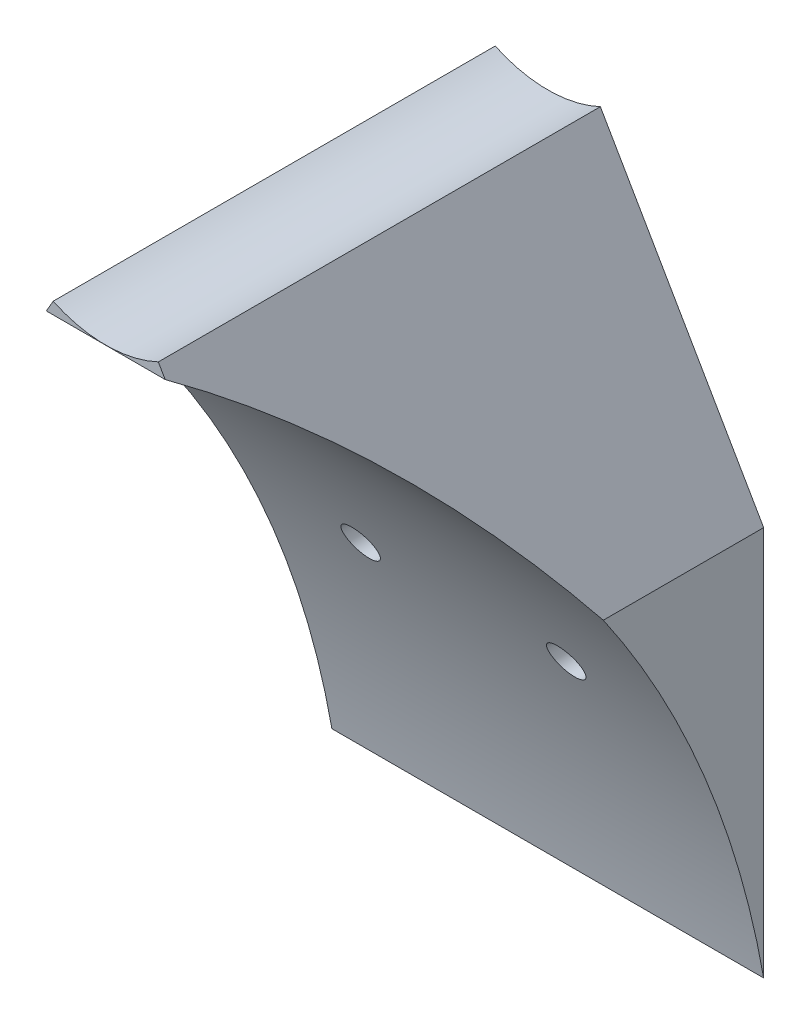
SolidWorks part; units mm, degrees
material "ABS"
ref_plane "Front Plane" through (0, 0, 0) normal (0, 0, 1) x (1, 0, 0)
ref_plane "Top Plane" through (0, 0, 0) normal (0, 1, 0) x (1, 0, 0)
ref_plane "Right Plane" through (0, 0, 0) normal (1, 0, 0) x (0, 0, -1)
sketch "Sketch1" plane through (0, 0, 0) normal (0, 0, 1) x (1, 0, 0)
  line L0 (0, 0) -> (0, -127) construction
  line L1 (0, 0) -> (38.1, -65.9911) construction
  line L2 (0, 0) -> (-38.1, -65.9911) construction
  line L3 (-38.1, -65.9911) -> (-38.1, -121.1503) construction
  line L5 (0, 0) -> (0, -127) construction
  line L6 (38.1, -121.1503) -> (38.1, -65.9911) construction
  line L7 (38.1, -121.1503) -> (38.1, -159.2503) construction
  line L8 (-50.8, -197.3503) -> (0, -197.3503) construction
  line L9 (-50.8, -195.7628) -> (0, -195.7628) construction
  line L10 (36.5125, -121.1503) -> (36.5125, -159.2503) construction
  line L11 (36.5125, -121.1503) -> (36.5125, -66.4165)
  line L12 (0, -3.175) -> (36.5125, -66.4165)
  line L13 (0, -3.175) -> (-36.5125, -66.4165)
  line L14 (-36.5125, -66.4165) -> (-36.5125, -121.1503)
  line L15 (-36.5125, -121.1503) -> (-38.1, -121.1503) construction
  line L16 (-50.8, -195.7628) -> (-50.8, -197.3503) construction
  line L17 (36.5125, -121.1503) -> (-36.5125, -121.1503)
  circle A0 centre (0, 0) radius 127 construction
  circle A1 centre (0, 0) radius 76.2 construction
  arc A2 (38.1, -159.2503) -> (0, -197.3503) centre (0, -159.2503) cw construction
  arc A3 (36.5125, -159.2503) -> (0, -195.7628) centre (0, -159.2503) cw construction
  point P2 (-15.875, -74.528)
  point P12 (0, 0)
  point P14 (15.875, -74.528)
  point P25 (0, -38.1)
  dimension "D2" = 152.4
  dimension "D6" = 1.5875
  dimension "D1" = 127
  dimension "D3" = 38.1
  dimension "D4" = 50.8
  dimension "D5" = 60
  dimension "D7" = 38.1
  dimension "D8" = 31.75
extrude "Boss-Extrude1" add sketch "Sketch1" along normal blind 76.2
sketch "Sketch2" plane through (0, 0, 0) normal (1, 0, 0) x (0, 0, -1)
  line L3 (-76.2, -121.1503) -> (0, -121.1503) construction
  line L4 (-76.2, -121.1503) -> (-76.2, -66.4165) construction
  line L6 (-76.2, -121.1503) -> (0, -121.1503)
  line L7 (-76.2, -121.1503) -> (-76.2, -66.4165)
  line L10 (-76.2, -66.4165) -> (-76.2, -3.175) construction
  line L11 (-76.2, -22.225) -> (-76.2, -66.4165)
  line L12 (0, -66.4165) -> (0, -3.175) construction
  line L13 (-76.2, -3.175) -> (0, -3.175) construction
  line L14 (-68.2625, -19.0675) -> (-68.2625, -3.175)
  line L15 (-68.2625, -3.175) -> (-76.2, -3.175)
  line L16 (-76.2, -3.175) -> (-76.2, -22.225)
  arc A0 (-68.2625, -19.0675) -> (0, -121.1503) centre (-150.0796, -147.6432) cw
  dimension "D1" = 68.2625
  dimension "D2" = 152.4
extrude "Cut-Extrude1" cut sketch "Sketch2" along normal up to surface (36.5125 mm away) from surface up to face at (36.5125, -93.7834, 38.1) starting at face at (-36.5125, -93.7834, 38.1)
sketch "Sketch5" plane through (0, 0, 0) normal (0, 0, 1) x (1, 0, 0)
  line L0 (0, -82.55) -> (0, 0) construction
  circle A0 centre (0, 0) radius 82.55 construction
  point P0 (0, -38.1)
  point P4 (-15.875, -81.0092)
  point P5 (15.875, -81.0092)
  dimension "D1" = 38.1
  dimension "D3" = 165.1
  dimension "D2" = 31.75
hole_wizard "M5 Clearance Hole1" positions "Sketch7" profile "Sketch8" hole size "M5" standard "ANSI Metric" end condition through all
sketch "Sketch7" plane through (0, 0, 0) normal (0, 0, -1) x (-1, 0, 0)
  point P0 (-15.875, -81.0092)
  point P3 (15.875, -81.0092)
  point P6 (0, -38.1)
sketch "Sketch8" plane through (15.875, -81.0092, 0) normal (1, 0, 0) x (0, 1, 0)
  line L0 (0, 0) -> (0, 68.2625)
  line L1 (0, 68.2625) -> (2.75, 68.2625)
  line L2 (2.75, 68.2625) -> (2.75, 0)
  line L5 (2.75, 0) -> (0, 0)
  line L11 (0, -6.35) -> (0, 107.95) construction
  dimension "Thru Hole Dia." = 5.5
  dimension "Thru Hole Depth" = 68.2625
sketch "Sketch10" plane through (0, 0, 0) normal (0, 0, -1) x (-1, 0, 0)
  circle A0 centre (0, 0) radius 19.05
  dimension "D1" = 38.1
extrude "Cut-Extrude2" cut sketch "Sketch10" against normal up to next
sketch "Sketch11" plane through (0, 0, 0) normal (0, 0, -1) x (-1, 0, 0)
  line L0 (-33.3375, -60.9172) -> (-33.3375, -121.1503)
  line L1 (-36.5125, -66.4165) -> (-8.1171, -17.2342) construction
  line L2 (36.5125, -121.1503) -> (-36.5125, -121.1503) construction
  line L3 (33.3375, -60.9172) -> (33.3375, -121.1503)
  line L4 (8.1171, -17.2342) -> (36.5125, -66.4165) construction
  line L5 (33.3375, -121.1503) -> (36.5125, -121.1503)
  line L10 (36.5125, -66.4165) -> (8.1171, -17.2342)
  line L11 (-8.1171, -17.2342) -> (-36.5125, -66.4165)
  line L12 (-36.5125, -66.4165) -> (-36.5125, -121.1503)
  line L13 (-36.5125, -121.1503) -> (36.5125, -121.1503)
  line L14 (36.5125, -121.1503) -> (36.5125, -66.4165)
  line L15 (36.5125, -66.4165) -> (33.3375, -60.9172)
  line L16 (-33.3375, -60.9172) -> (-36.5125, -66.4165)
  line L17 (-36.5125, -66.4165) -> (-36.5125, -121.1503)
  line L18 (-36.5125, -121.1503) -> (-33.3375, -121.1503)
  line L19 (36.5125, -121.1503) -> (36.5125, -66.4165)
  arc A1 (-8.1171, -17.2342) -> (8.1171, -17.2342) centre (0, 0) ccw
  dimension "D2" = 3.175
  dimension "D3" = 3.175
  dimension "D1" = 0
extrude "Cut-Extrude3" cut sketch "Sketch11" against normal through all
